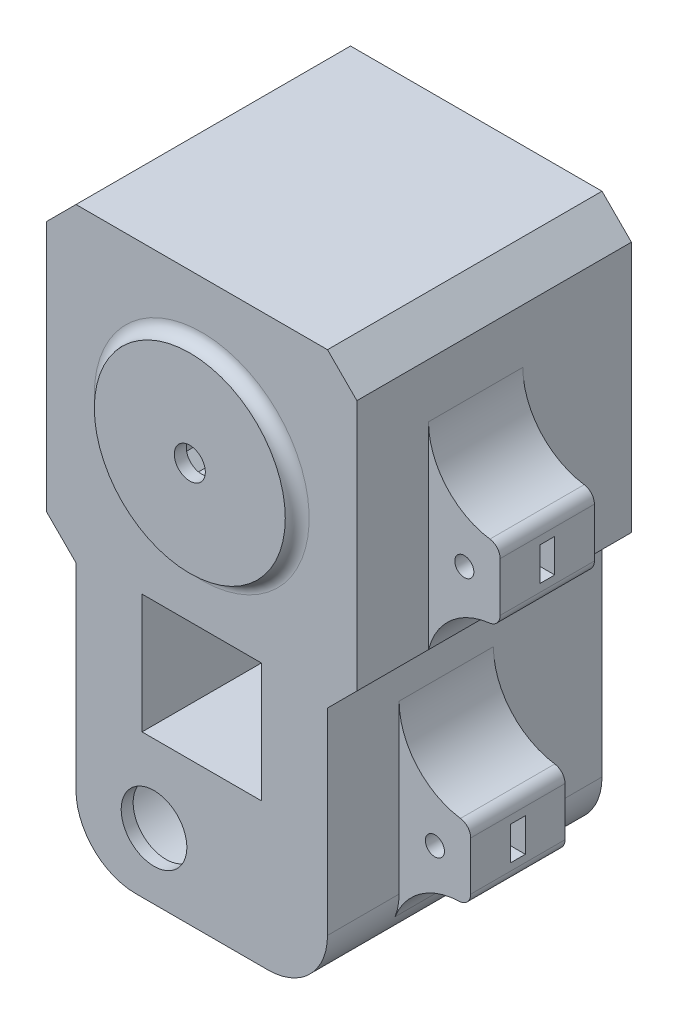
SolidWorks part; units mm, degrees
ref_plane "Alzado" through (0, 0, 0) normal (0, 0, 1) x (1, 0, 0)
ref_plane "Planta" through (0, 0, 0) normal (0, 1, 0) x (1, 0, 0)
ref_plane "Vista lateral" through (0, 0, 0) normal (1, 0, 0) x (0, 0, -1)
sketch "Croquis1" plane through (0, 0, 0) normal (0, 0, 1) x (1, 0, 0)
  line L0 (-19, -21) -> (-21, -19)
  line L1 (19, -21) -> (-19, -21)
  line L2 (21, -19) -> (21, 19)
  line L3 (19, 21) -> (-19, 21)
  line L4 (-21, -19) -> (-21, 19)
  line L5 (21, -21) -> (-21, 21) construction
  line L6 (21, 21) -> (-21, -21) construction
  line L7 (-19, 21) -> (-21, 19)
  line L8 (21, 19) -> (19, 21)
  line L9 (21, -19) -> (19, -21)
  line L10 (26, -21.0711) -> (26, 21.0711)
  line L11 (26, 21.0711) -> (21.0711, 26)
  line L12 (21.0711, 26) -> (-21.0711, 26)
  line L13 (-21.0711, 26) -> (-26, 21.0711)
  line L14 (-26, -21.0711) -> (-26, 21.0711)
  line L15 (-21.0711, -26) -> (-26, -21.0711)
  line L16 (21.0711, -26) -> (-21.0711, -26)
  line L17 (26, -21.0711) -> (21.0711, -26)
  point P0 (0, 0)
  dimension "D1" = 42
  dimension "D2" = 42
  dimension "D3" = 5
extrude "Saliente-Extruir1" add sketch "Croquis1" along normal mid plane 44
sketch "Croquis2" plane through (0, -26, 0) normal (0, -1, 0) x (1, 0, 0)
  line L4 (-21.0711, -22) -> (21.0711, -22)
  line L5 (21.0711, -22) -> (21.0711, 22)
  line L6 (21.0711, 22) -> (-21.0711, 22)
  line L7 (-21.0711, 22) -> (-21.0711, -22)
  line L8 (-21.0711, -22) -> (21.0711, -22)
  line L9 (21.0711, -22) -> (21.0711, 22)
  line L10 (21.0711, 22) -> (-21.0711, 22)
  line L11 (-21.0711, 22) -> (-21.0711, -22)
  dimension "D1" = 0
extrude "Saliente-Extruir2" add sketch "Croquis2" along normal blind 8
sketch "Croquis3" plane through (0, 0, 0) normal (0, 0, 1) x (1, 0, 0)
  line L0 (-19, -21) -> (19, -21) construction
  line L1 (-16.8806, -21) -> (16.8806, -21)
  line L2 (-16.8806, -21) -> (-16.8806, -29)
  line L3 (-16.8806, -29) -> (16.8806, -29)
  line L4 (16.8806, -21) -> (16.8806, -29)
  line L5 (0, 18.4155) -> (0, -35.026) construction
  dimension "D1" = 33.7612
  dimension "D2" = 8
extrude "Cortar-Extruir1" cut sketch "Croquis3" against normal through all contours L2 L1 L4 L3
sketch "Croquis4" plane through (0, 0, 22) normal (0, 0, -1) x (-1, 0, 0)
  line L10 (-26, -21.0711) -> (-21.0711, -26)
  line L11 (-21.0711, -26) -> (-21.0711, -34)
  line L12 (-21.0711, -34) -> (21.0711, -34)
  line L13 (21.0711, -34) -> (21.0711, -26)
  line L14 (21.0711, -26) -> (26, -21.0711)
  line L15 (26, -21.0711) -> (26, 21.0711)
  line L16 (26, 21.0711) -> (21.0711, 26)
  line L17 (21.0711, 26) -> (-21.0711, 26)
  line L18 (-21.0711, 26) -> (-26, 21.0711)
  line L19 (-26, 21.0711) -> (-26, -21.0711)
  line L20 (-26, -21.0711) -> (-21.0711, -26)
  line L21 (-21.0711, -26) -> (-21.0711, -34)
  line L22 (-21.0711, -34) -> (21.0711, -34)
  line L23 (21.0711, -34) -> (21.0711, -26)
  line L24 (21.0711, -26) -> (26, -21.0711)
  line L25 (26, -21.0711) -> (26, 21.0711)
  line L26 (26, 21.0711) -> (21.0711, 26)
  line L27 (21.0711, 26) -> (-21.0711, 26)
  line L28 (-21.0711, 26) -> (-26, 21.0711)
  line L29 (-26, 21.0711) -> (-26, -21.0711)
  circle A0 centre (0, 0) radius 11
  dimension "D2" = 22
  dimension "D1" = 0
extrude "Saliente-Extruir4" add sketch "Croquis4" against normal blind 2
sketch "Croquis7" plane through (0, 0, 24) normal (0, 0, 1) x (1, 0, 0)
  circle A0 centre (0, 0) radius 2.6
  circle A3 centre (0, 0) radius 16
  circle A4 centre (0, 0) radius 16
  dimension "D2" = 5.2
  dimension "D1" = 5
extrude "Saliente-Extruir5" add sketch "Croquis7" along normal blind 2
sketch "Croquis6" plane through (0, -29, 0) normal (0, 1, 0) x (1, 0, 0)
  line L0 (0, -24.5904) -> (0, 23.7869) construction
  line L1 (-14, 18) -> (14, 18)
  line L2 (-14, 18) -> (-14, 6)
  line L3 (-14, 6) -> (14, 6)
  line L4 (14, 18) -> (14, 6)
  dimension "D1" = 28
  dimension "D2" = 12
  dimension "D3" = 18
extrude "Cortar-Extruir3" cut sketch "Croquis6" against normal blind 13
sketch "Croquis8" plane through (0, 0, 0) normal (0, 0, 1) x (1, 0, 0)
  line L0 (-26, -21.0711) -> (-26, 21.0711)
  line L1 (-26, -21.0711) -> (-26, 21.0711)
  line L2 (-26, 21.0711) -> (-21.0711, 26)
  line L3 (-26, 21.0711) -> (-21.0711, 26)
  line L4 (-21.0711, 26) -> (21.0711, 26)
  line L5 (-21.0711, 26) -> (21.0711, 26)
  line L6 (21.0711, 26) -> (26, 21.0711)
  line L7 (21.0711, 26) -> (26, 21.0711)
  line L8 (26, 21.0711) -> (26, -21.0711)
  line L9 (26, 21.0711) -> (26, -21.0711)
  line L10 (26, -21.0711) -> (21.0711, -26)
  line L11 (26, -21.0711) -> (21.0711, -26)
  line L12 (21.0711, -26) -> (21.0711, -34)
  line L13 (21.0711, -26) -> (21.0711, -34)
  line L14 (21.0711, -34) -> (-21.0711, -34)
  line L15 (21.0711, -34) -> (-21.0711, -34)
  line L16 (-21.0711, -34) -> (-21.0711, -26)
  line L17 (-21.0711, -34) -> (-21.0711, -26)
  line L18 (-21.0711, -26) -> (-26, -21.0711)
  line L19 (-21.0711, -26) -> (-26, -21.0711)
  line L20 (0, 0) -> (-39.949, 0) construction
  line L21 (0, 0) -> (0, 31.7363) construction
  line L22 (26, -12) -> (38, -12)
  line L23 (-26, 0) -> (-38, 0)
  line L24 (-26, 0) -> (-26, -12)
  line L25 (-26, -12) -> (-38, -12)
  line L26 (-38, 0) -> (-38, -12)
  line L27 (38, 0) -> (38, -12)
  line L28 (26, 0) -> (38, 0)
  line L29 (26, 0) -> (26, -12)
  line L30 (-38, -12) -> (-26, 0) construction
  circle A0 centre (-32, -6) radius 1.6
  circle A1 centre (32, -6) radius 1.6
  dimension "D3" = 3.2
  dimension "D1" = 12
  dimension "D2" = 12
extrude "Saliente-Extruir6" add sketch "Croquis8" along normal blind 12 and the other way blind 3.8 contours L23 L26 L25 L1 | L28 L9 L22 L27 region at (-32, -11.8303, 0) region at (26.1697, -6, 0)
sketch "Croquis9" plane through (38, 0, 0) normal (1, 0, 0) x (0, 0, -1)
  line L0 (3.8, -6) -> (-12, -6) construction
  line L1 (3.8, 0) -> (3.8, -12) construction
  line L2 (-12, 0) -> (-12, -12) construction
  line L4 (-2.85, -3.2) -> (-5.35, -3.2)
  line L5 (-2.85, -3.2) -> (-2.85, -8.8)
  line L6 (-2.85, -8.8) -> (-5.35, -8.8)
  line L7 (-5.35, -3.2) -> (-5.35, -8.8)
  line L8 (-2.85, -3.2) -> (-5.35, -8.8) construction
  line L9 (-2.85, -8.8) -> (-5.35, -3.2) construction
  point P6 (-4.1, -6)
  dimension "D1" = 5.6
  dimension "D2" = 2.5
extrude "Cortar-Extruir4" cut sketch "Croquis9" against normal blind 10
mirror "Simetría1" about plane through (0, 0, 0) normal (1, 0, 0) of "Cortar-Extruir4"
sketch "Croquis11" plane through (0, -34, 0) normal (0, -1, 0) x (1, 0, 0)
  line L4 (-21.0711, 24) -> (-21.0711, -22)
  line L5 (-21.0711, -22) -> (21.0711, -22)
  line L6 (21.0711, -22) -> (21.0711, 24)
  line L7 (21.0711, 24) -> (-21.0711, 24)
  line L8 (-21.0711, 24) -> (-21.0711, -22)
  line L9 (-21.0711, -22) -> (21.0711, -22)
  line L10 (21.0711, -22) -> (21.0711, 24)
  line L11 (21.0711, 24) -> (-21.0711, 24)
  dimension "D1" = 0
extrude "Saliente-Extruir8" add sketch "Croquis11" along normal blind 35
sketch "Croquis12" plane through (0, 0, -22) normal (0, 0, -1) x (-1, 0, 0)
  line L0 (0, 0) -> (0, -75.996) construction
  line L1 (18.0711, -66) -> (-18.0711, -66)
  line L2 (18.0711, -66) -> (18.0711, -38)
  line L3 (18.0711, -38) -> (-18.0711, -38)
  line L4 (-18.0711, -66) -> (-18.0711, -38)
  line L5 (21.0711, -69) -> (21.0711, -26) construction
  line L6 (21.0711, -69) -> (-21.0711, -69) construction
  dimension "D1" = 3
  dimension "D2" = 3
  dimension "D3" = 28
extrude "Cortar-Extruir5" cut sketch "Croquis12" against normal offset from surface (44 mm away) 2 up to face at (-16, 0, 24)
sketch "Croquis14" plane through (0, 0, 24) normal (0, 0, 1) x (1, 0, 0)
  line L0 (0, 0) -> (0, -70.2297) construction
  line L1 (10, -25) -> (-10, -25)
  line L2 (10, -25) -> (10, -45)
  line L3 (10, -45) -> (-10, -45)
  line L4 (-10, -25) -> (-10, -45)
  line L5 (10, -25) -> (-10, -45) construction
  line L6 (10, -45) -> (-10, -25) construction
  point P0 (0, -35)
  dimension "D1" = 35
  dimension "D2" = 20
  dimension "D3" = 20
extrude "Cortar-Extruir7" cut sketch "Croquis14" against normal blind 25
sketch "Croquis15" plane through (0, 0, 22) normal (0, 0, -1) x (-1, 0, 0)
  line L0 (-10, -38) -> (-18.0711, -38)
  line L1 (-18.0711, -38) -> (-18.0711, -49)
  line L2 (-18.0711, -49) -> (18.0711, -49)
  line L3 (18.0711, -49) -> (18.0711, -38)
  line L4 (18.0711, -38) -> (10, -38)
  line L5 (10, -38) -> (10, -45)
  line L6 (10, -45) -> (-10, -45)
  line L7 (-10, -45) -> (-10, -38)
  dimension "D1" = 4
  dimension "D2" = 90
  dimension "D3" = 90
extrude "Saliente-Extruir9" add sketch "Croquis15" along normal blind 25
sketch "Croquis16" plane through (0, 0, -3) normal (0, 0, -1) x (-1, 0, 0)
  line L1 (-10, -45) -> (10, -45)
  line L2 (-10, -45) -> (-10, -25)
  line L3 (-10, -25) -> (10, -25)
  line L4 (10, -45) -> (10, -25)
extrude "Saliente-Extruir11" add sketch "Croquis16" against normal blind 3.2
sketch "Croquis17" plane through (0, -49, 0) normal (0, -1, 0) x (1, 0, 0)
  line L0 (0, -10) -> (0, 26) construction
  line L1 (16, 26) -> (-16, 26) construction
  circle A0 centre (0, 8) radius 1.6
  point P6 (0, 0)
  dimension "D1" = 3.2
  dimension "D2" = 8
extrude "Cortar-Extruir8" cut sketch "Croquis17" against normal blind 40
sketch "Croquis18" plane through (0, -21, 0) normal (0, 1, 0) x (1, 0, 0)
  circle A0 centre (0, -8) radius 1.6 construction
  circle A1 centre (0, -8) radius 1.6
  circle A2 centre (0, -8) radius 4.8
  dimension "D1" = 3.2
extrude "Cortar-Extruir9" cut sketch "Croquis18" against normal blind 2
sketch "Croquis13" plane through (0, 0, 22) normal (0, 0, -1) x (-1, 0, 0)
  line L0 (18.0711, -52) -> (-18.0711, -52) construction
  line L1 (18.0711, -66) -> (18.0711, -38) construction
  line L2 (-18.0711, -38) -> (-18.0711, -66) construction
  line L3 (0, 0) -> (0, -68.0761) construction
  circle A0 centre (8, -58) radius 5.5
  point P8 (0, 0)
  point P9 (-8.0054, -58.5)
  point P13 (10.141, -58.5)
  dimension "D1" = 11
  dimension "D3" = 11
  dimension "D2" = 6
  dimension "D4" = 8
extrude "Cortar-Extruir6" cut sketch "Croquis13" against normal blind 2
fillet "Redondeo1" radius 10 2 edges at (-18.0711, -66, 0) (18.0711, -66, 0)
fillet "Redondeo2" radius 10 2 edges at (-21.0711, -69, 1) (21.0711, -69, 1)
sketch "Croquis19" plane through (21.0711, 0, 0) normal (1, 0, 0) x (0, 0, -1)
  line L0 (0, 0) -> (0, -69) construction
  line L1 (22, -69) -> (-24, -69) construction
  line L2 (3.8, 0) -> (3.8, -12) construction
  line L3 (3.8, -55) -> (-12, -55)
  line L4 (3.8, -55) -> (3.8, -43)
  line L5 (3.8, -43) -> (-12, -43)
  line L6 (-12, -55) -> (-12, -43)
  line L7 (-12, 0) -> (-12, -12) construction
  line L8 (-2.85, -8.8) -> (-2.85, -3.2) construction
  line L9 (-2.85, -51.8) -> (-5.35, -51.8)
  line L10 (-2.85, -51.8) -> (-2.85, -46.2)
  line L11 (-2.85, -46.2) -> (-5.35, -46.2)
  line L12 (-5.35, -51.8) -> (-5.35, -46.2)
  line L13 (-5.35, -3.2) -> (-5.35, -8.8) construction
  line L14 (3.8, -49) -> (-12, -49) construction
  dimension "D1" = 12
  dimension "D2" = 43
  dimension "D3" = 5.6
extrude "Saliente-Extruir12" add sketch "Croquis19" along normal blind 12
sketch "Croquis20" plane through (0, 0, -3.8) normal (0, 0, -1) x (-1, 0, 0)
  line L0 (-33.0711, -49) -> (-21.0711, -49) construction
  line L1 (-33.0711, -55) -> (-33.0711, -43) construction
  line L2 (-21.0711, -59) -> (-21.0711, -26) construction
  line L3 (-27.0711, -55) -> (-27.0711, -43) construction
  line L4 (-33.0711, -55) -> (-21.0711, -55) construction
  line L5 (-33.0711, -43) -> (-21.0711, -43) construction
  circle A0 centre (-27.0711, -49) radius 1.6
  dimension "D1" = 3.2
extrude "Cortar-Extruir10" cut sketch "Croquis20" against normal through all
mirror "Simetría2" about plane through (0, 0, 0) normal (1, 0, 0) of "Saliente-Extruir12", "Cortar-Extruir10"
fillet "Redondeo3" radius 12 4 edges at (21.0711, -55, 4.1) (26, -12, 4.1) (26, 0, 4.1) (21.0711, -43, 4.1)
fillet "Redondeo4" radius 2 4 edges at (33.0711, -55, 4.1) (33.0711, -43, 4.1) (38, -12, 4.1) (38, 0, 4.1)
fillet "Redondeo5" radius 10 4 edges at (-21.0711, -55, 4.1) (-21.0711, -43, 4.1) (-26, -12, 4.1) (-26, 0, 4.1)
fillet "Redondeo6" radius 2 4 edges at (-33.0711, -43, 4.1) (-38, 0, 4.1) (-38, -12, 4.1) (-33.0711, -55, 4.1)
fillet "Redondeo7" radius 2 1 edges at (-16, 0, 24)
